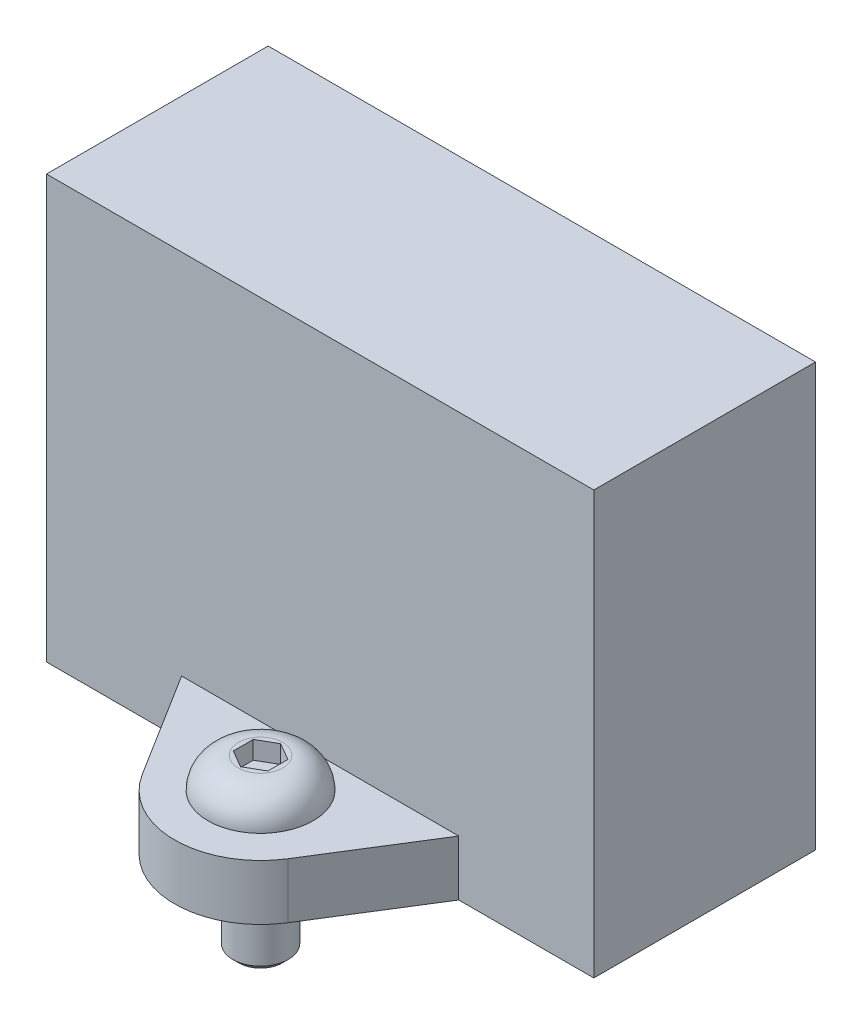
SolidWorks part; units mm, degrees
ref_plane "前视基准面" through (0, 0, 0) normal (0, 0, 1) x (1, 0, 0)
ref_plane "上视基准面" through (0, 0, 0) normal (0, 1, 0) x (1, 0, 0)
ref_plane "右视基准面" through (0, 0, 0) normal (1, 0, 0) x (0, 0, -1)
ref_plane "基准面4" through (0, 0, 0) normal (0, 1, 0) x (1, 0, 0)
sketch "草图1" plane through (0, 0, 0) normal (0, 1, 0) x (1, 0, 0)
  line L0 (-19.75, 0) -> (19.75, 0)
  line L1 (19.75, 0) -> (19.75, 16)
  line L2 (19.75, 16) -> (-19.75, 16)
  line L3 (-19.75, 16) -> (-19.75, 0)
extrude "凸台-拉伸1" add sketch "草图1" along normal blind 30.5
sketch "草图2" plane through (0, 0, 0) normal (0, 1, 0) x (1, 0, 0)
  line L0 (-10, 0) -> (-5.2572, -7.5866)
  line L1 (5.2572, -7.5866) -> (10, 0)
  line L2 (10, 0) -> (-10, 0)
  arc A0 (-5.2572, -7.5866) -> (5.2572, -7.5866) centre (0, -4.3) ccw
extrude "凸台-拉伸2" add sketch "草图2" along normal blind 4
ref_plane "基准面5" through (0, 0, 4.3) normal (0, 0, 1) x (1, 0, 0)
sketch "草图3" plane through (0, 0, 4.3) normal (0, 0, 1) x (1, 0, 0)
  line L0 (0, 4) -> (2.15, 4)
  line L1 (2.15, 4) -> (2.15, 0)
  line L2 (2.15, 0) -> (0, 0)
  line L3 (0, 0) -> (0, 4)
  line L4 (0, 0) -> (0, 4) construction
revolve "切除-旋转1" cut sketch "草图3" angle 360 about L4 reverse direction yes
ref_plane "基准面6" through (0, 0, 4.3) normal (0, 0, 1) x (1, 0, 0)
sketch "草图4" plane through (0, 0, 4.3) normal (0, 0, 1) x (1, 0, 0)
  line L0 (0, 6.2) -> (1.6, 6.2)
  line L1 (3.8, 4) -> (2, 4)
  line L2 (2, 4) -> (2, -5.5705)
  line L3 (2, -5.5705) -> (1.5705, -6)
  line L4 (1.5705, -6) -> (0, -6)
  line L5 (0, -6) -> (0, 6.2)
  line L6 (0, -6) -> (0, 6.2) construction
  arc A0 (1.6, 6.2) -> (3.8, 4) centre (1.6, 4) cw
revolve "旋转1" add sketch "草图4" angle 360 about L6 reverse direction yes
cosmetic thread "装饰螺纹线1" parameters "D1"=8.6, "D2"=3.141
ref_plane "基准面7" through (0, 6.2, 0) normal (0, 1, 0) x (1, 0, 0)
sketch "草图5" plane through (0, 6.2, 0) normal (0, 1, 0) x (1, 0, 0)
  line L0 (-1.25, -3.5783) -> (-1.25, -5.0217)
  line L1 (-1.25, -5.0217) -> (0, -5.7434)
  line L2 (0, -5.7434) -> (1.25, -5.0217)
  line L3 (1.25, -5.0217) -> (1.25, -3.5783)
  line L4 (1.25, -3.5783) -> (0, -2.8566)
  line L5 (0, -2.8566) -> (-1.25, -3.5783)
extrude "切除-拉伸1" cut sketch "草图5" against normal blind 1.3
ref_plane "基准面8" through (0, 0, 0) normal (0, 1, 0) x (1, 0, 0)
ref_plane "to_motor_cover XY" through (0, 0, 0) normal (0, -1, 0) x (-1, 0, 0)
ref_plane "to_motor_cover XZ" through (0, 0, 4.3) normal (0, 0, -1) x (-1, 0, 0)
ref_plane "to_motor_cover YZ" through (0, 0, 0) normal (1, 0, 0) x (0, 0, -1)
ref_axis "to_motor_cover X" through (-80.9, 0, 4.3) along (1, 0, 0)
ref_axis "to_motor_cover Y" through (0, 0, -50) along (0, 0, 1)
ref_axis "to_motor_cover Z" through (0, -50, 4.3) along (0, 1, 0)
sketch3d "to_motor_cover"
  point P0 (0, 0, 4.3)
